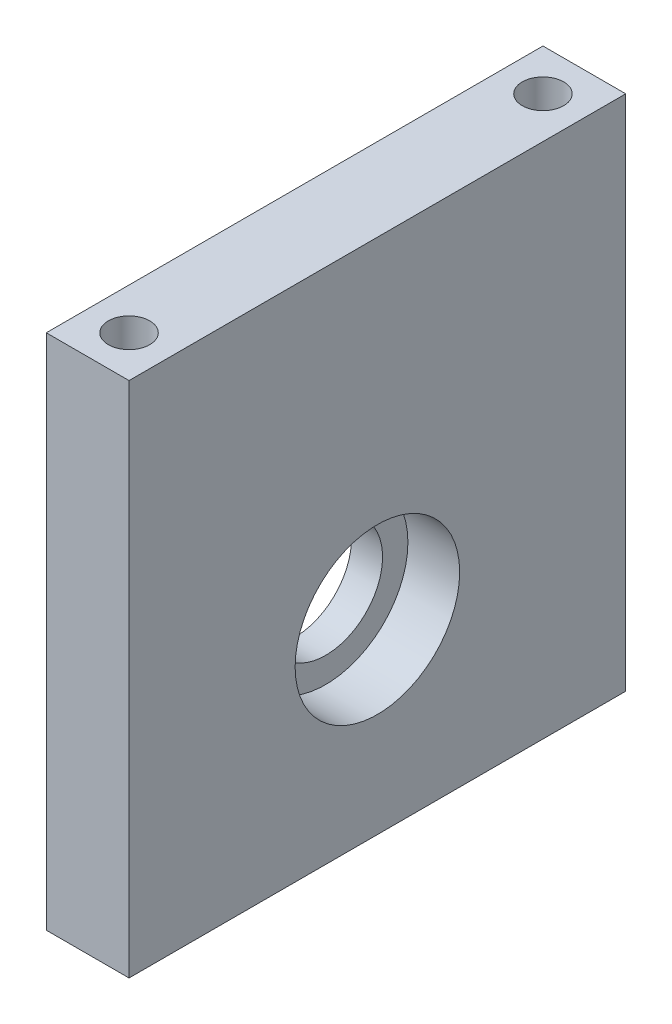
SolidWorks part; units mm, degrees
ref_plane "Plan de face" through (0, 0, 0) normal (0, 0, 1) x (1, 0, 0)
ref_plane "Plan de dessus" through (0, 0, 0) normal (0, 1, 0) x (1, 0, 0)
ref_plane "Plan de droite" through (0, 0, 0) normal (1, 0, 0) x (0, 0, -1)
sketch "Esquisse1" plane through (0, 0, 0) normal (0, 1, 0) x (1, 0, 0)
  line L17 (0, 0) -> (8, 0)
  line L19 (8, 0) -> (8, 48)
  line L20 (8, 48) -> (0, 48)
  line L21 (0, 48) -> (0, 0)
extrude "Boss.-Extru.1" add sketch "Esquisse1" along normal blind 50 contours L20 L21 L17 L19 region at (4, 0, -24)
sketch "Esquisse28" plane through (8, 0, 0) normal (1, 0, 0) x (0, 0, -1)
  line L0 (0, 0) -> (24, 0) construction
  line L1 (0, 0) -> (48, 0) construction
  line L2 (24, 0) -> (24, 18) construction
  circle A0 centre (24, 18) radius 7.95
  dimension "D1" = 15.9
  dimension "D2" = 18
  dimension "D3" = 24
extrude "Enlèv. mat.-Extru.1" cut sketch "Esquisse28" against normal blind 10
sketch "Esquisse29" plane through (0, 0, 0) normal (-1, 0, 0) x (0, 0, 1)
  circle A0 centre (-24, 18) radius 8.2
  circle A1 centre (-24, 18) radius 5.5
extrude "Boss.-Extru.2" add sketch "Esquisse29" against normal blind 3
sketch "Esquisse30" plane through (0, 0, 0) normal (0, -1, 0) x (1, 0, 0)
  line L0 (0, 0) -> (8, 0) construction
  line L1 (8, 0) -> (8, -8) construction
  line L2 (8, 0) -> (8, -48) construction
  line L3 (8, -8) -> (0, -8) construction
  line L4 (0, -48) -> (0, 0) construction
  line L5 (0, -8) -> (0, 0) construction
  line L6 (0, 0) -> (8, -8) construction
  line L7 (8, -8) -> (8, 0) construction
  line L8 (8, 0) -> (0, -8) construction
  line L9 (0, -48) -> (8, -48) construction
  line L10 (8, -48) -> (8, -40) construction
  line L11 (8, -40) -> (0, -40) construction
  line L12 (0, -48) -> (0, -40) construction
  line L13 (0, -40) -> (8, -48) construction
  line L14 (8, -48) -> (8, -40) construction
  line L15 (8, -40) -> (0, -48) construction
  circle A0 centre (4, -44) radius 2
  circle A1 centre (4, -4) radius 2
extrude "Enlèv. mat.-Extru.2" cut sketch "Esquisse30" against normal blind 15
sketch "Esquisse31" plane through (0, 50, 0) normal (0, 1, 0) x (1, 0, 0)
  line L0 (0, 0) -> (8, 0) construction
  line L1 (8, 0) -> (8, 48) construction
  line L2 (0, 0) -> (8, 0) construction
  line L3 (8, 0) -> (8, 8) construction
  line L4 (8, 8) -> (0, 8) construction
  line L5 (0, 48) -> (0, 0) construction
  line L6 (0, 8) -> (0, 0) construction
  line L7 (0, 0) -> (8, 8) construction
  line L8 (8, 8) -> (8, 0) construction
  line L9 (8, 0) -> (0, 8) construction
  line L10 (0, 48) -> (8, 48) construction
  line L11 (8, 48) -> (8, 40) construction
  line L12 (8, 40) -> (0, 40) construction
  line L13 (0, 40) -> (0, 48) construction
  line L14 (0, 48) -> (8, 40) construction
  line L15 (8, 40) -> (8, 48) construction
  line L16 (8, 48) -> (0, 40) construction
  circle A0 centre (4, 44) radius 2
  circle A1 centre (4, 4) radius 2
extrude "Enlèv. mat.-Extru.3" cut sketch "Esquisse31" against normal blind 15
